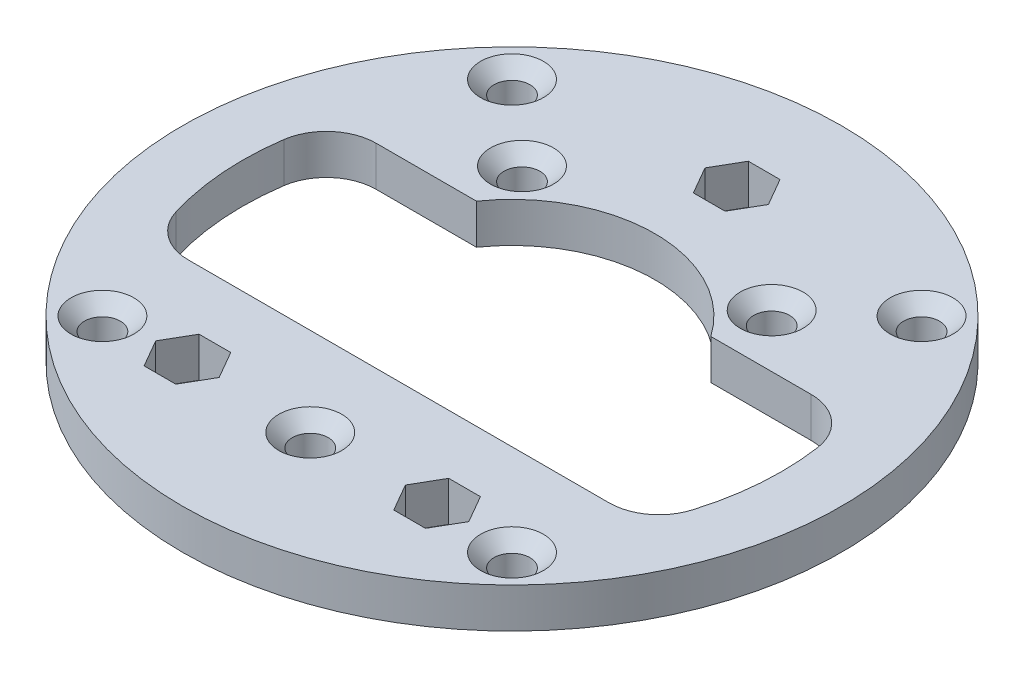
SolidWorks part; units mm, degrees
material "PEI"
ref_plane "Front Plane" through (0, 0, 0) normal (0, 0, 1) x (1, 0, 0)
ref_plane "Top Plane" through (0, 0, 0) normal (0, 1, 0) x (1, 0, 0)
ref_plane "Right Plane" through (0, 0, 0) normal (1, 0, 0) x (0, 0, -1)
sketch "Sketch1" plane through (0, 0, 0) normal (0, 1, 0) x (1, 0, 0)
  circle A0 centre (0, 0) radius 33
  circle A1 centre (0, 0) radius 27
  dimension "D1" = 66
  dimension "D2" = 6
extrude "Boss-Extrude1" add sketch "Sketch1" along normal blind 4
sketch "Sketch2" plane through (0, 4, 0) normal (0, 1, 0) x (1, 0, 0)
  line L0 (-24.5, -11.3468) -> (24.5, -11.3468)
  line L1 (-25.7325, 8.1755) -> (-11.7325, 8.1755)
  line L2 (0, 0) -> (7.7557, 0) construction
  line L3 (11.7325, 8.1755) -> (25.7325, 8.1755)
  line L4 (-20.5061, 20.5061) -> (0, 0) construction
  line L5 (-12.5, 13.5) -> (12.5, 13.5) construction
  circle A0 centre (0, 22.5) radius 2.25 construction
  circle A1 centre (-12.5, -20) radius 2.25 construction
  circle A2 centre (12.5, -20) radius 2.25 construction
  circle A4 centre (-12.5, 13.5) radius 1.5
  circle A6 centre (0, 0) radius 27 construction
  arc A8 (-11.7325, 8.1755) -> (11.7325, 8.1755) centre (0, 0) cw
  arc A9 (25.7325, 8.1755) -> (-25.7325, 8.1755) centre (0, 0) ccw
  arc A10 (24.5, -11.3468) -> (-24.5, -11.3468) centre (0, 0) cw
  circle A11 centre (12.5, 13.5) radius 1.5
  circle A12 centre (0, 0) radius 29 construction
  circle A13 centre (0, 0) radius 33 construction
  circle A14 centre (-20.5061, 20.5061) radius 1.75 construction
  circle A15 centre (20.5061, 20.5061) radius 1.75 construction
  circle A16 centre (20.5061, -20.5061) radius 1.75 construction
  circle A17 centre (-20.5061, -20.5061) radius 1.75 construction
  circle A18 centre (0, -20.2) radius 1.5
  point P15 (0, 13.5)
  point P19 (0, 0)
  point P44 (0, 0)
  circle M2 centre (0, 0) radius 27
  dimension "D5" = 4.5
  dimension "D6" = 4.5
  dimension "D7" = 4.5
  dimension "D12" = 14.3
  dimension "D16" = 3.5
  dimension "D11" = 3
  dimension "D1" = 25
  dimension "D2" = 12.5
  dimension "D3" = 22.5
  dimension "D4" = 20
  dimension "D14" = 4
  dimension "D15" = 135
  dimension "D8" = 14
  dimension "D9" = 14
  dimension "D10" = 49
  dimension "D18" = 25
  dimension "D19" = 20.2
  dimension "D13" = 13.5
  dimension "D17" = 4
extrude "Saliente-Extruir1" add sketch "Sketch2" against normal up to surface (4 mm away) contours L1 A8 L3 M2 | L0 M2 region at (0, 4, 17.7643) region at (0, 4, -16.947) up to face at (0, 0, 33)
sketch "Croquis1" plane through (0, 4, 0) normal (0, 1, 0) x (1, 0, 0)
  line L1 (-9.3246, -20) -> (-10.9123, -17.25)
  line L2 (-10.9123, -17.25) -> (-14.0877, -17.25)
  line L3 (-14.0877, -17.25) -> (-15.6754, -20)
  line L4 (-15.6754, -20) -> (-14.0877, -22.75)
  line L5 (-14.0877, -22.75) -> (-10.9123, -22.75)
  line L6 (-10.9123, -22.75) -> (-9.3246, -20)
  line L7 (15.6754, -20) -> (14.0877, -17.25)
  line L8 (14.0877, -17.25) -> (10.9123, -17.25)
  line L9 (10.9123, -17.25) -> (9.3246, -20)
  line L10 (9.3246, -20) -> (10.9123, -22.75)
  line L11 (10.9123, -22.75) -> (14.0877, -22.75)
  line L12 (14.0877, -22.75) -> (15.6754, -20)
  line L13 (3.1754, 22.5) -> (1.5877, 25.25)
  line L14 (1.5877, 25.25) -> (-1.5877, 25.25)
  line L15 (-1.5877, 25.25) -> (-3.1754, 22.5)
  line L16 (-3.1754, 22.5) -> (-1.5877, 19.75)
  line L17 (-1.5877, 19.75) -> (1.5877, 19.75)
  line L18 (1.5877, 19.75) -> (3.1754, 22.5)
  circle A0 centre (-20.5061, 20.5061) radius 1.75 construction
  circle A1 centre (-20.5061, 20.5061) radius 1.75
  circle A4 centre (20.5061, 20.5061) radius 1.75 construction
  circle A5 centre (20.5061, 20.5061) radius 1.75
  circle A6 centre (-12.5, -20) radius 2.75 construction
  circle A7 centre (12.5, -20) radius 2.75 construction
  circle A8 centre (0, 22.5) radius 2.75 construction
  circle A16 centre (-20.5061, -20.5061) radius 1.75 construction
  circle A17 centre (-20.5061, -20.5061) radius 1.75
  circle A18 centre (20.5061, -20.5061) radius 1.75 construction
  circle A19 centre (20.5061, -20.5061) radius 1.75
  dimension "D1" = 5.5
  dimension "D2" = 5.5
  dimension "D3" = 5.5
extrude "Cortar-Extruir1" cut sketch "Croquis1" against normal up to next
hole_wizard "CSK for M3 Flat Head Machine Screw1" positions "Sketch4" profile "Sketch5" countersink size "M3" standard "ANSI Metric" end condition through all
sketch "Sketch4" plane through (0, 4, 0) normal (0, 1, 0) x (1, 0, 0)
  point P0 (-20.5061, 20.5061)
  point P3 (20.5061, 20.5061)
  point P6 (20.5061, -20.5061)
  point P9 (-20.5061, -20.5061)
sketch "Sketch5" plane through (-20.5061, 4, -20.5061) normal (1, 0, 0) x (0, 0, 1)
  line L0 (0, 0) -> (0, 4)
  line L1 (0, 4) -> (1.8, 4)
  line L2 (1.8, 4) -> (1.8, 1.35)
  line L3 (1.8, 1.35) -> (3.15, 0)
  line L5 (3.15, 0) -> (0, 0)
  line L6 (-1.8, 1.35) -> (-3.15, 0) construction
  line L11 (0, -6.35) -> (0, 107.95) construction
  dimension "Thru Hole Dia." = 3.6
  dimension "Thru Hole Depth" = 4
  dimension "Near C'Sink Dia." = 6.3
  dimension "Near C'Sink Angle" = 90
hole_wizard "CSK for M3 Flat Head Machine Screw2" positions "Sketch6" profile "Sketch7" countersink size "M3" standard "ANSI Metric" end condition through all
sketch "Sketch6" plane through (0, 4, 0) normal (0, 1, 0) x (1, 0, 0)
  point P12 (-12.5, 13.5)
  point P15 (12.5, 13.5)
  point P18 (0, -20.2)
sketch "Sketch7" plane through (-12.5, 4, -13.5) normal (1, 0, 0) x (0, 0, 1)
  line L0 (0, 0) -> (0, 4)
  line L1 (0, 4) -> (1.8, 4)
  line L2 (1.8, 4) -> (1.8, 1.35)
  line L3 (1.8, 1.35) -> (3.15, 0)
  line L5 (3.15, 0) -> (0, 0)
  line L6 (-1.8, 1.35) -> (-3.15, 0) construction
  line L11 (0, -6.35) -> (0, 107.95) construction
  dimension "Thru Hole Dia." = 3.6
  dimension "Thru Hole Depth" = 4
  dimension "Near C'Sink Dia." = 6.3
  dimension "Near C'Sink Angle" = 90
fillet "Fillet1" radius 5 4 edges at (-25.7325, 2, -8.1755) (25.7325, 2, -8.1755) (24.5, 2, 11.3468) (-24.5, 2, 11.3468)
equation "\"D2@Sketch2\"=\"D1@Sketch2\"/2"
equation "\"D6@Sketch2\"=\"D5@Sketch2\""
equation "\"D7@Sketch2\"=\"D6@Sketch2\""
equation "\"D2@Croquis1\"=\"D3@Croquis1\""
equation "\"D1@Croquis1\"=\"D3@Croquis1\""
